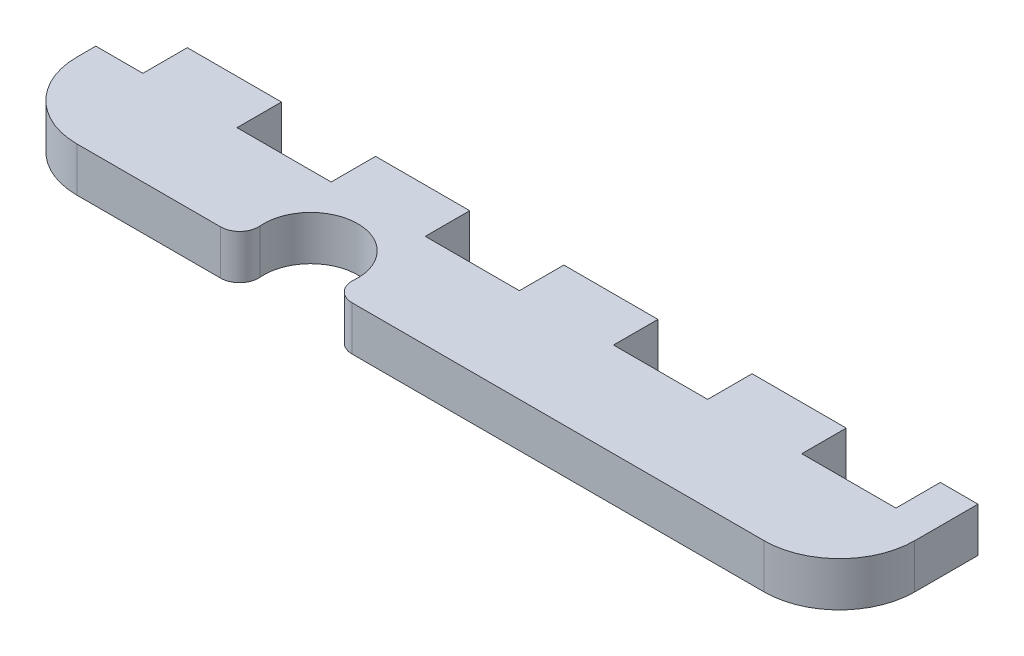
SolidWorks part; units mm, degrees
ref_plane "Front Plane" through (0, 0, 0) normal (0, 0, 1) x (1, 0, 0)
ref_plane "Top Plane" through (0, 0, 0) normal (0, 1, 0) x (1, 0, 0)
ref_plane "Right Plane" through (0, 0, 0) normal (1, 0, 0) x (0, 0, -1)
sketch "Sketch1" plane through (0, 0, 0) normal (0, 1, 0) x (1, 0, 0)
  line L0 (0, 0) -> (12.7, 0)
  line L1 (12.7, 0) -> (12.7, -5.9944)
  line L2 (12.7, -5.9944) -> (25.4, -5.9944)
  line L3 (0, 0) -> (0, -5.9944)
  line L4 (25.4, 0) -> (38.1, 0)
  line L5 (38.1, 0) -> (38.1, -5.9944)
  line L6 (38.1, -5.9944) -> (50.8, -5.9944)
  line L7 (25.4, 0) -> (25.4, -5.9944)
  line L8 (50.8, 0) -> (63.5, 0)
  line L9 (63.5, 0) -> (63.5, -5.9944)
  line L10 (63.5, -5.9944) -> (76.2, -5.9944)
  line L11 (50.8, 0) -> (50.8, -5.9944)
  line L12 (76.2, 0) -> (88.9, 0)
  line L13 (88.9, 0) -> (88.9, -5.9944)
  line L14 (88.9, -5.9944) -> (101.6, -5.9944)
  line L15 (76.2, 0) -> (76.2, -5.9944)
  line L16 (101.6, 0) -> (106.68, 0)
  line L17 (106.68, 0) -> (106.68, -5.9944)
  line L18 (0, -5.9944) -> (-6.35, -5.9944)
  line L19 (101.6, 0) -> (101.6, -5.9944)
  line L20 (114.3, -5.9944) -> (127, -5.9944) [skipped]
  line L21 (101.6, 0) -> (114.3, 0) [skipped]
  line L22 (114.3, 0) -> (114.3, -5.9944) [skipped]
  line L23 (-6.35, -5.9944) -> (-6.35, -8.5344)
  line L24 (3.81, -18.6944) -> (23.2021, -18.6944)
  line L25 (106.68, -8.5344) -> (106.68, -5.9944)
  line L26 (40.9209, -18.6944) -> (96.52, -18.6944)
  arc A0 (96.52, -18.6944) -> (106.68, -8.5344) centre (96.52, -8.5344) ccw
  arc A1 (-6.35, -8.5344) -> (3.81, -18.6944) centre (3.81, -8.5344) ccw
  arc A2 (38.3896, -15.9438) -> (25.7334, -15.9438) centre (32.0615, -15.4174) ccw
  arc A3 (25.7334, -15.9438) -> (23.2021, -18.6944) centre (23.2021, -16.1544) cw
  arc A4 (38.3896, -15.9438) -> (40.9209, -18.6944) centre (40.9209, -16.1544) ccw
  point P42 (37.5006, -18.6944)
  dimension "D2" = 10.16
  dimension "D3" = 10.16
  dimension "D4" = 2.54
  dimension "D5" = 2.54
  dimension "D1" = 5
extrude "Boss-Extrude1" add sketch "Sketch1" along normal blind 5.9944
